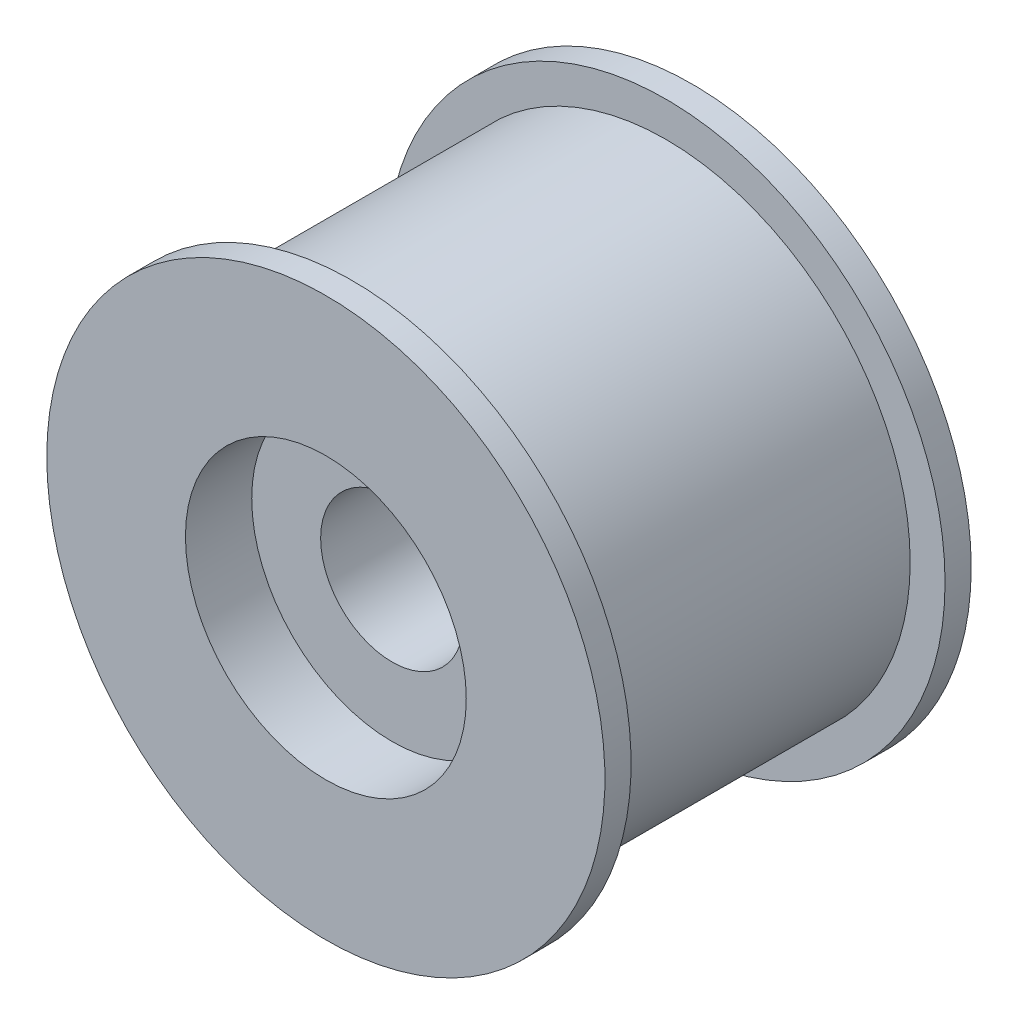
SolidWorks part; units mm, degrees
ref_plane "Front Plane" through (0, 0, 0) normal (0, 0, 1) x (1, 0, 0)
ref_plane "Top Plane" through (0, 0, 0) normal (0, 1, 0) x (1, 0, 0)
ref_plane "Right Plane" through (0, 0, 0) normal (1, 0, 0) x (0, 0, -1)
sketch "Sketch1" plane through (0, 0, 0) normal (0, 0, 1) x (1, 0, 0)
  circle A0 centre (0, 0) radius 14
  circle A1 centre (0, 0) radius 4.1
  dimension "D1" = 28
  dimension "D2" = 8.2
extrude "Boss-Extrude1" add sketch "Sketch1" along normal blind 21
sketch "Sketch8" plane through (0, 0, 21) normal (0, 0, -1) x (-1, 0, 0)
  circle A0 centre (0, 0) radius 16
  circle A1 centre (0, 0) radius 6.25
  dimension "D1" = 32
  dimension "D2" = 12.5
extrude "Boss-Extrude2" add sketch "Sketch8" along normal blind 1.5
sketch "Sketch9" plane through (0, 0, 0) normal (0, 0, 1) x (1, 0, 0)
  circle A0 centre (0, 0) radius 16
  circle A1 centre (0, 0) radius 6.25
  dimension "D1" = 12.5
  dimension "D2" = 32
extrude "Boss-Extrude3" add sketch "Sketch9" along normal blind 1.5
sketch "Sketch10" plane through (0, 0, 21) normal (0, 0, 1) x (1, 0, 0)
  circle A0 centre (0, 0) radius 8.05
  dimension "D1" = 16.1
extrude "Cut-Extrude1" cut sketch "Sketch10" against normal blind 3.8
extrude "Cut-Extrude2" cut sketch "Sketch10<2>" along normal blind 3.8 from surface starting at face at (16, 0, 0)
sketch "Sketch10<2>" plane through (0, 0, 21) normal (0, 0, 1) x (1, 0, 0) same geometry as "Sketch10"
